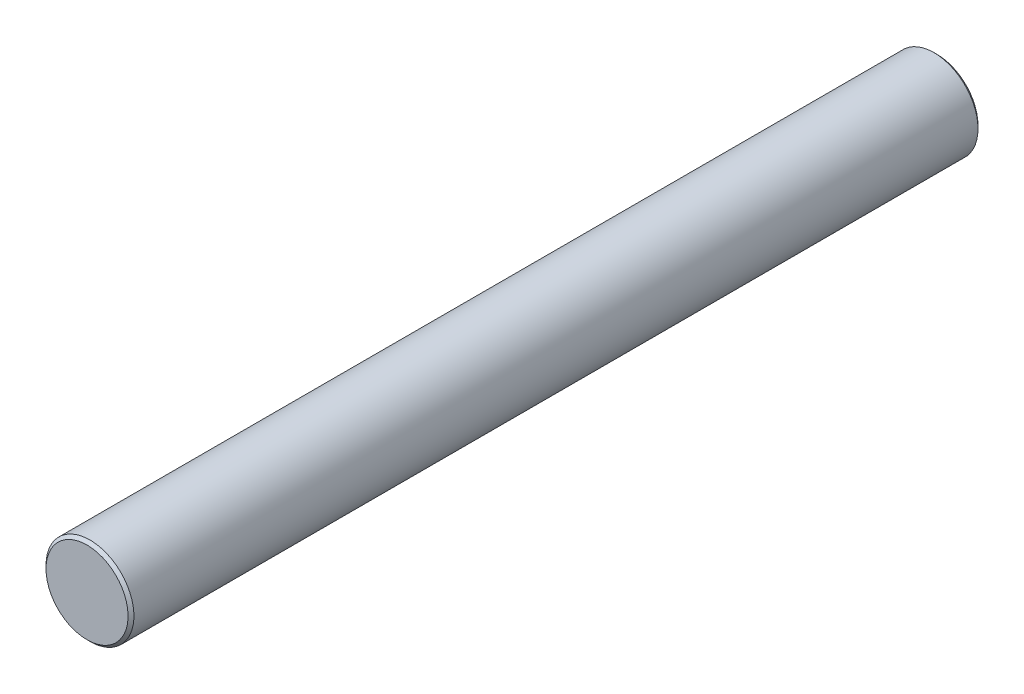
SolidWorks part; units mm, degrees
ref_plane "Front Plane" through (0, 0, 0) normal (0, 0, 1) x (1, 0, 0)
ref_plane "Top Plane" through (0, 0, 0) normal (0, 1, 0) x (1, 0, 0)
ref_plane "Right Plane" through (0, 0, 0) normal (1, 0, 0) x (0, 0, -1)
sketch "Sketch2" plane through (0, 0, 0) normal (0, 0, 1) x (1, 0, 0)
  circle A0 centre (0, 0) radius 0.75
  dimension "D1" = 1.5
extrude "Boss-Extrude1" add sketch "Sketch2" along normal blind 14.5
chamfer "Chamfer2" distance 0.05 angle 45 2 edges at (0.75, 0, 14.5) (0.75, 0, 0)
